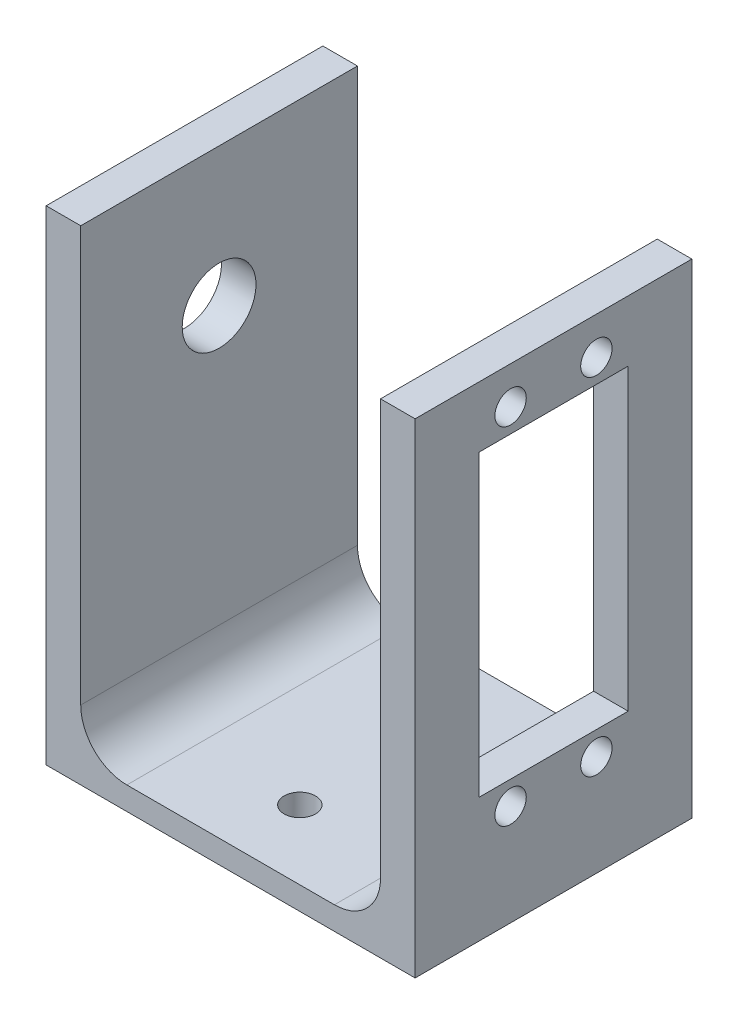
SolidWorks part; units mm, degrees
ref_plane "Front" through (0, 0, 0) normal (0, 0, 1) x (1, 0, 0)
ref_plane "Top" through (0, 0, 0) normal (0, 1, 0) x (1, 0, 0)
ref_plane "Right" through (0, 0, 0) normal (1, 0, 0) x (0, 0, -1)
sketch "Sketch1" plane through (0, 0, 0) normal (0, 1, 0) x (1, 0, 0)
  line L1 (0, 0) -> (50.8, 0)
  line L2 (0, 0) -> (0, 38.1)
  line L3 (0, 38.1) -> (50.8, 38.1)
  line L4 (50.8, 0) -> (50.8, 38.1)
  dimension "D1" = 38.1
  dimension "D2" = 50.8
extrude "Boss-Extrude1" add sketch "Sketch1" along normal blind 3.175
sketch "Sketch2" plane through (0, 3.175, 0) normal (0, 1, 0) x (1, 0, 0)
  line L0 (0, 0) -> (50.8, 0) construction
  line L1 (50.8, 38.1) -> (46.0375, 38.1)
  line L2 (50.8, 38.1) -> (50.8, 0)
  line L3 (50.8, 0) -> (46.0375, 0)
  line L4 (46.0375, 38.1) -> (46.0375, 0)
  line L5 (50.8, 38.1) -> (0, 38.1) construction
  line L6 (4.7625, 38.1) -> (0, 38.1)
  line L7 (4.7625, 38.1) -> (4.7625, 0)
  line L8 (4.7625, 0) -> (0, 0)
  line L9 (0, 38.1) -> (0, 0)
  dimension "D1" = 4.7625
extrude "Boss-Extrude2" add sketch "Sketch2" along normal blind 63.5
fillet "Fillet1" radius 6.35 2 edges at (4.7625, 3.175, -19.05) (46.0375, 3.175, -19.05)
sketch "Sketch3" plane through (50.8, 0, 0) normal (1, 0, 0) x (0, 0, -1)
  line L0 (0, 0) -> (38.1, 0) construction
  line L1 (38.1, 66.675) -> (38.1, 0) construction
  line L2 (0, 66.675) -> (38.1, 66.675) construction
  line L5 (8.763, 58.293) -> (29.337, 58.293)
  line L6 (8.763, 58.293) -> (8.763, 17.145)
  line L7 (8.763, 17.145) -> (29.337, 17.145)
  line L8 (29.337, 58.293) -> (29.337, 17.145)
  point P0 (19.05, 10.3505)
  point P8 (19.05, 65.0875)
  point P9 (19.05, 66.675)
  point P14 (19.05, 17.145)
  point P15 (29.337, 37.719)
  point P16 (28.8925, 37.719)
  line B0 (28.8925, 65.0875) -> (28.8925, 10.3505) construction
  line B1 (28.8925, 65.0875) -> (9.2075, 65.0875) construction
  line B2 (9.2075, 65.0875) -> (9.2075, 10.3505) construction
  circle B3 centre (24.9555, 61.5315) radius 2.159
  circle B4 centre (13.1445, 61.5315) radius 2.159
  circle B5 centre (13.1445, 13.9065) radius 2.159
  circle B6 centre (24.9555, 13.9065) radius 2.159
  dimension "D1" = 1.5875
  dimension "D2" = 41.148
  dimension "D3" = 20.574
sketch_block_instance "ServoMountingHoles-1"
sketch_block "ServoMountingHoles"
extrude "Cut-Extrude1" cut sketch "Sketch3" against normal up to next
sketch "Sketch4" plane through (0, 3.175, 0) normal (0, 1, 0) x (1, 0, 0)
  line L0 (25.4, 28.575) -> (25.4, 9.525) construction
  line L1 (11.1125, 19.05) -> (39.6875, 19.05) construction
  line L2 (11.1125, 38.1) -> (11.1125, 0) construction
  line L3 (39.6875, 0) -> (39.6875, 38.1) construction
  circle A0 centre (25.4, 28.575) radius 2.159
  circle A1 centre (25.4, 9.525) radius 2.159
  point P10 (25.4, 19.05)
  dimension "D1" = 19.05
  dimension "D2" = 4.318
extrude "Cut-Extrude2" cut sketch "Sketch4" against normal up to next
sketch "Sketch5" plane through (0, 0, 0) normal (-1, 0, 0) x (0, 0, 1)
  line L0 (-38.1, 66.675) -> (0, 66.675) construction
  circle A0 centre (-19.05, 47.625) radius 5.08
  point P4 (-19.05, 66.675)
  dimension "D1" = 19.05
extrude "Cut-Extrude3" cut sketch "Sketch5" against normal up to next
